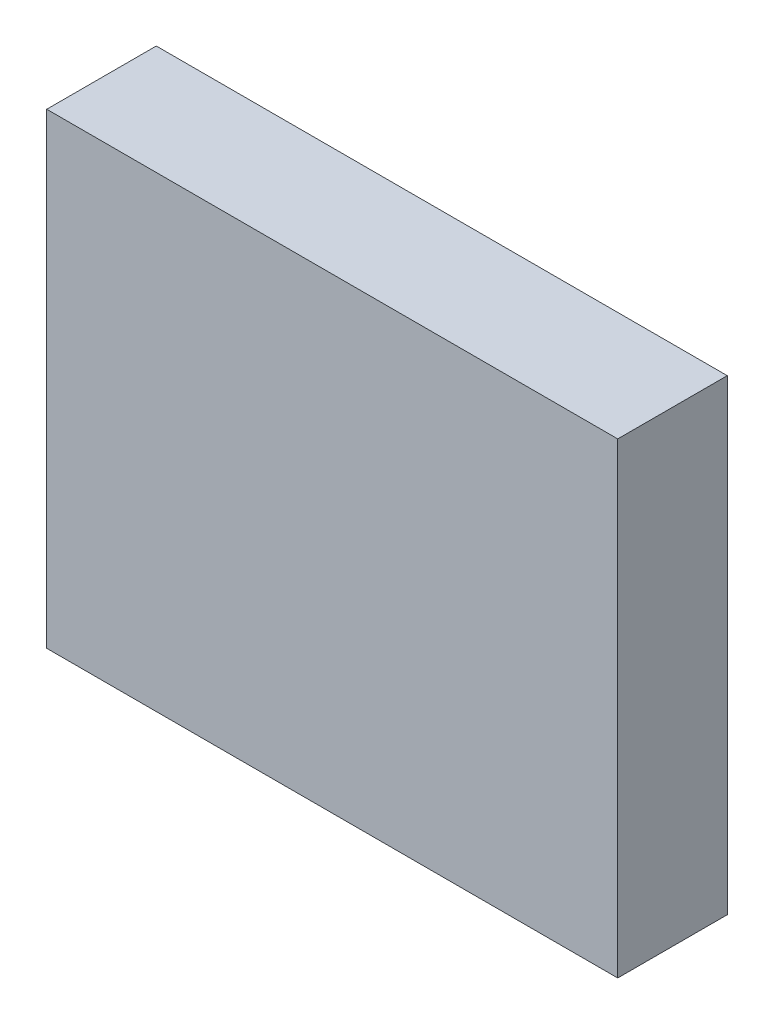
SolidWorks part; units mm, degrees
material "Aço"
ref_plane "Plano superior" through (0, 0, 0) normal (0, 0, 1) x (1, 0, 0)
ref_plane "Plano frontal" through (0, 0, 0) normal (0, 1, 0) x (1, 0, 0)
ref_plane "Plano direito" through (0, 0, 0) normal (1, 0, 0) x (0, 0, -1)
other "Caixa delimitadora"
ref_plane "Default Plane" through (-78.1989, -63.94, 0) normal (0, 1, 0) x (1, 0, 0)
sketch "Esboço1" plane through (0, 0, 0) normal (0, 0, 1) x (1, 0, 0)
  line L1 (-78.1989, -63.94) -> (78.1989, -63.94)
  line L2 (-78.1989, -63.94) -> (-78.1989, 63.94)
  line L3 (-78.1989, 63.94) -> (78.1989, 63.94)
  line L4 (78.1989, -63.94) -> (78.1989, 63.94)
  line L5 (-78.1989, -63.94) -> (78.1989, 63.94) construction
  line L6 (-78.1989, 63.94) -> (78.1989, -63.94) construction
  point P0 (0, 0)
extrude "Ressalto-extrusão1" add sketch "Esboço1" along normal blind 30
